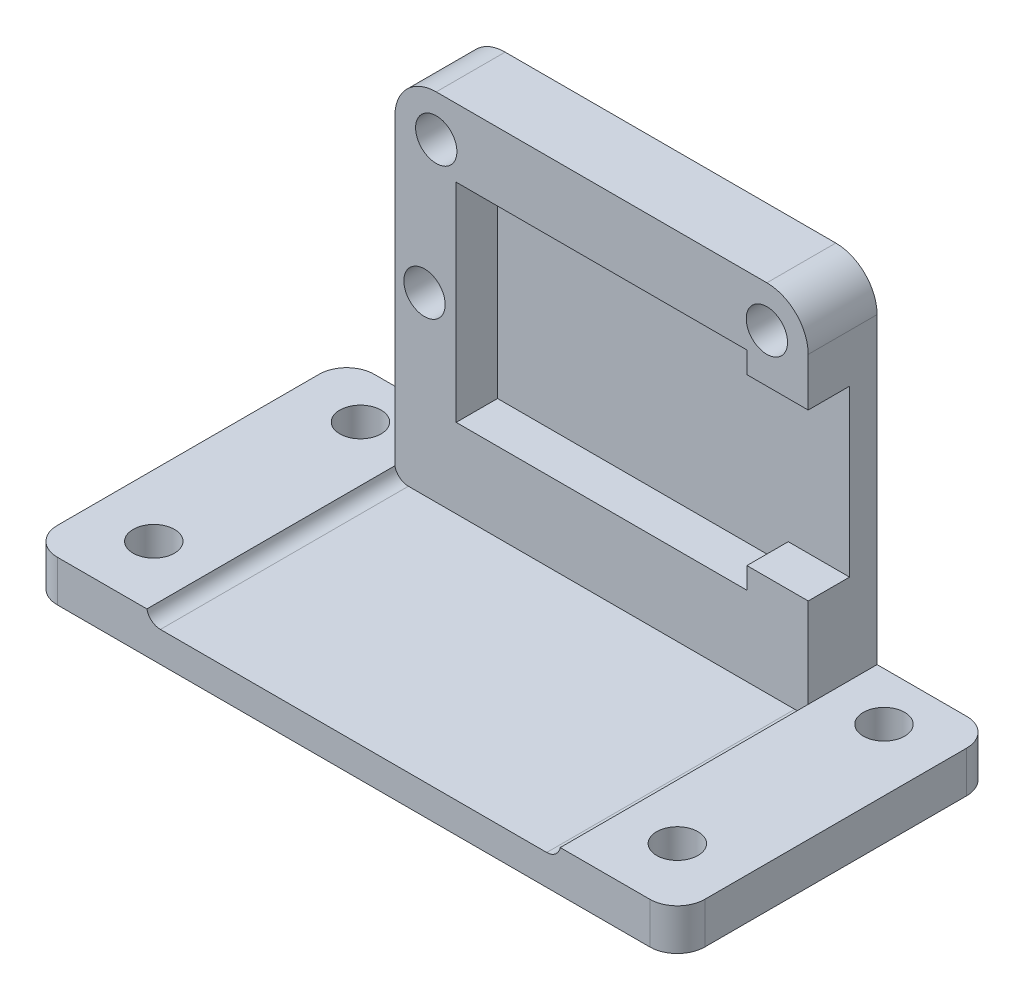
SolidWorks part; units mm, degrees
ref_plane "前视基准面" through (0, 0, 0) normal (0, 0, 1) x (1, 0, 0)
ref_plane "上视基准面" through (0, 0, 0) normal (0, 1, 0) x (1, 0, 0)
ref_plane "右视基准面" through (0, 0, 0) normal (1, 0, 0) x (0, 0, -1)
sketch "草图1" plane through (0, 0, 0) normal (0, 0, 1) x (1, 0, 0)
  line L1 (15, -12.5) -> (-15, -12.5)
  line L2 (15, -12.5) -> (15, 12.5)
  line L3 (15, 12.5) -> (-15, 12.5)
  line L4 (-15, -12.5) -> (-15, 12.5)
  line L5 (15, -12.5) -> (-15, 12.5) construction
  line L6 (15, 12.5) -> (-15, -12.5) construction
  point P0 (0, 0)
  dimension "D1" = 30
  dimension "D2" = 25
extrude "凸台-拉伸1" add sketch "草图1" along normal blind 5
sketch "草图2" plane through (0, 0, 5) normal (0, 0, 1) x (1, 0, 0)
  line L1 (10.55, -7.55) -> (-10.55, -7.55)
  line L2 (10.55, -7.55) -> (10.55, 7.55)
  line L3 (10.55, 7.55) -> (-10.55, 7.55)
  line L4 (-10.55, -7.55) -> (-10.55, 7.55)
  line L5 (10.55, -7.55) -> (-10.55, 7.55) construction
  line L6 (10.55, 7.55) -> (-10.55, -7.55) construction
  point P0 (0, 0)
  dimension "D1" = 21.1
  dimension "D2" = 15.1
extrude "切除-拉伸1" cut sketch "草图2" against normal blind 3
sketch "草图3" plane through (0, 0, 5) normal (0, 0, 1) x (1, 0, 0)
  line L0 (12.775, 0) -> (0, 0) construction
  line L1 (15, -6) -> (10.55, -6)
  line L2 (15, -6) -> (15, 6)
  line L3 (15, 6) -> (10.55, 6)
  line L4 (10.55, -6) -> (10.55, 6)
  line L5 (15, -6) -> (10.55, 6) construction
  line L6 (15, 6) -> (10.55, -6) construction
  line L7 (10.55, -7.55) -> (10.55, 7.55) construction
  line L8 (15, -12.5) -> (15, 12.5) construction
  point P0 (12.775, 0)
  dimension "D1" = 12
extrude "切除-拉伸2" cut sketch "草图3" against normal up to surface (3 mm away) up to face at (0, 0, 2)
fillet "圆角3" radius 3 2 edges at (15, 12.5, 2.5) (-15, 12.5, 2.5)
sketch "草图8" plane through (0, 0, 2) normal (0, 0, 1) x (1, 0, 0)
  line L0 (-10.55, -7.55) -> (10.55, -7.55) construction
  line L1 (-10.55, 7.55) -> (-10.55, -7.55) construction
  circle A0 centre (12, 9.5) radius 1.5
  circle A1 centre (-12, 9.5) radius 1.5
  circle A2 centre (-12.85, -0.55) radius 1.5
  dimension "D1" = 3
  dimension "D2" = 3
  dimension "D3" = 2.3
  dimension "D5" = 3
  dimension "D4" = 7
extrude "切除-拉伸6" cut sketch "草图8" against normal mid plane 20
sketch "草图9" plane through (0, -12.5, 0) normal (0, -1, 0) x (1, 0, 0)
  line L1 (-23.5, 0) -> (23.5, 0)
  line L2 (-23.5, 0) -> (-23.5, 23)
  line L3 (-23.5, 23) -> (23.5, 23)
  line L4 (23.5, 0) -> (23.5, 23)
  dimension "D1" = 23
  dimension "D2" = 47
  dimension "D3" = 23.5
extrude "凸台-拉伸2" add sketch "草图9" along normal blind 3
sketch "草图10" plane through (0, -12.5, 0) normal (0, 1, 0) x (1, 0, 0)
  circle A0 centre (-19, -3.5) radius 1.5
  circle A1 centre (19, -3.5) radius 1.5
  circle A2 centre (-19, -18.5) radius 1.5
  circle A3 centre (19, -18.5) radius 1.5
  dimension "D3" = 3
  dimension "D4" = 3
  dimension "D1" = 38
  dimension "D2" = 19
  dimension "D5" = 2
extrude "切除-拉伸7" cut sketch "草图10" against normal through all
fillet "圆角4" radius 2 4 edges at (23.5, -14, 0) (23.5, -14, 23) (-23.5, -14, 0) (-23.5, -14, 23)
sketch "草图11" plane through (0, 0, 23) normal (0, 0, 1) x (1, 0, 0)
  line L1 (-15, -12.5) -> (15, -12.5)
  line L2 (-15, -12.5) -> (-15, -13.3)
  line L3 (-15, -13.3) -> (15, -13.3)
  line L4 (15, -12.5) -> (15, -13.3)
  dimension "D1" = 0.8
extrude "切除-拉伸8" cut sketch "草图11" against normal up to surface (18 mm away) up to face at (13.5, 9.5, 5)
fillet "圆角5" radius 1 2 edges at (15, -13.3, 14) (-15, -13.3, 14)
